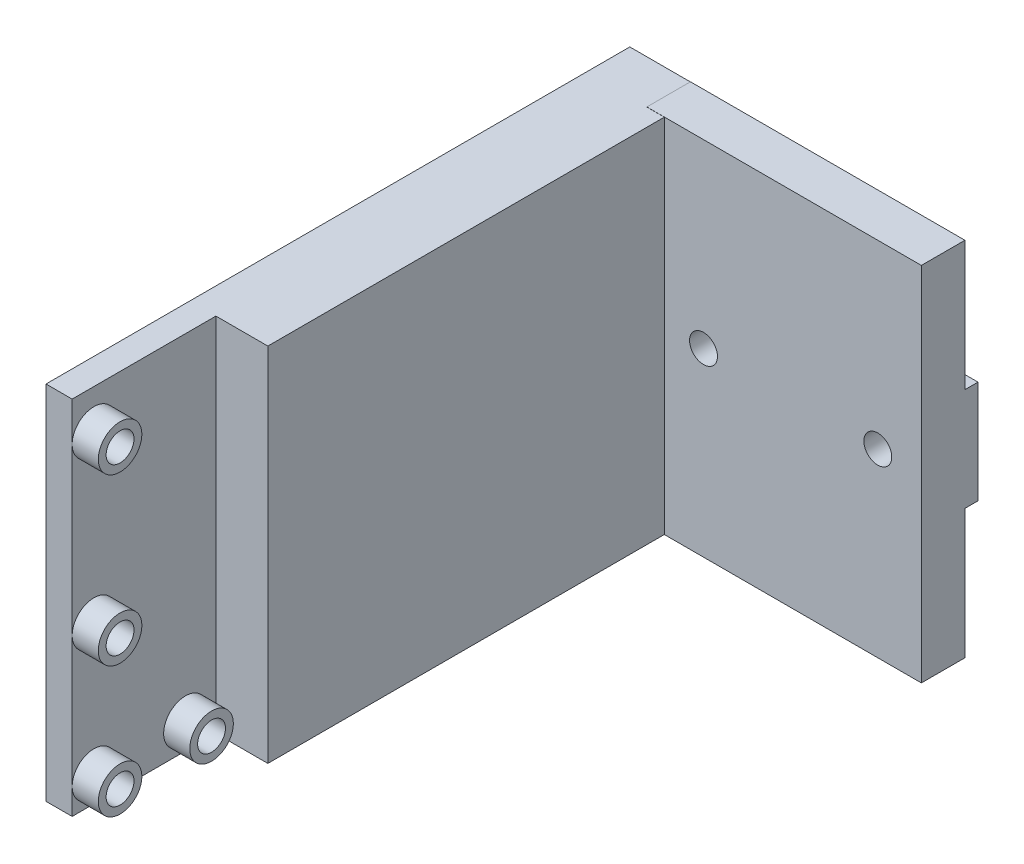
SolidWorks part; units mm, degrees
note: The reader was unsure of these and kept them because the rebuilt part matched: shared geometry of "Sketch4<6>".
ref_plane "Front Plane" through (0, 0, 0) normal (0, 0, 1) x (1, 0, 0)
ref_plane "Top Plane" through (0, 0, 0) normal (0, 1, 0) x (1, 0, 0)
ref_plane "Right Plane" through (0, 0, 0) normal (1, 0, 0) x (0, 0, -1)
sketch "Sketch1" plane through (0, 0, 0) normal (0, 0, 1) x (1, 0, 0)
  line L1 (-123.0401, -65.7341) -> (-91.5401, -65.7341)
  line L2 (-123.0401, -65.7341) -> (-123.0401, -107.2341)
  line L3 (-123.0401, -107.2341) -> (-91.5401, -107.2341)
  line L4 (-91.5401, -65.7341) -> (-91.5401, -107.2341)
  dimension "D2" = 41.5
  dimension "D1" = 31.5
extrude "Boss-Extrude1" add sketch "Sketch1" along normal blind 5
sketch "Sketch3" plane through (0, 0, 0) normal (0, 0, 1) x (1, 0, 0)
  line L1 (-123.0401, -65.75) -> (-129.0401, -65.75)
  line L2 (-123.0401, -65.75) -> (-123.0401, -107.2341)
  line L3 (-123.0401, -107.2341) -> (-129.0401, -107.2341)
  line L4 (-129.0401, -65.75) -> (-129.0401, -107.2341)
  line L6 (-123.0401, -107.2341) -> (-91.5401, -107.2341) construction
  line L7 (-123.0401, -65.7341) -> (-123.0401, -107.2341) construction
  dimension "D1" = 6
  dimension "D2" = 0
extrude "Boss-Extrude3" add sketch "Sketch3" along normal blind 50.5
sketch "Sketch5" plane through (0, 0, 50.5) normal (0, 0, 1) x (1, 0, 0)
  line L0 (-129.0401, -107.2341) -> (-123.0401, -107.2341) construction
  line L1 (-130, -65.75) -> (-127, -65.75)
  line L2 (-130, -65.75) -> (-130, -107.2341)
  line L3 (-130, -107.2341) -> (-127, -107.2341)
  line L4 (-127, -65.75) -> (-127, -107.2341)
  line L5 (-123.0401, -65.75) -> (-129.0401, -65.75) construction
  dimension "D1" = 0
  dimension "D2" = 3
  dimension "D3" = 0
extrude "Boss-Extrude4" add sketch "Sketch5" along normal blind 16.5
sketch "Sketch4" plane through (-127, 0, 0) normal (-1, 0, 0) x (0, 0, 1)
  line L0 (64.5, -104.25) -> (64.5, -70.25)
  line L3 (67, -107.2341) -> (67, -65.75) construction
  line L4 (54.5, -70.25) -> (64.5, -70.25)
  circle A0 centre (64.5, -70.25) radius 1.6
  circle A1 centre (64.5, -89.25) radius 1.6
  circle A2 centre (64.5, -104.25) radius 1.6
  circle A3 centre (54, -104.25) radius 1.6
  circle A4 centre (54, -104.25) radius 2.5
  circle A5 centre (64.5, -104.25) radius 2.5
  circle A6 centre (64.5, -89.25) radius 2.5
  circle A7 centre (64.5, -70.25) radius 2.5
  dimension "D1" = 3.2
  dimension "D2" = 3.2
  dimension "D3" = 3.2
  dimension "D4" = 3.2
  dimension "D5" = 5
  dimension "D6" = 5
  dimension "D7" = 5
  dimension "D8" = 5
  dimension "D10" = 15
  dimension "D13" = 19
  dimension "D9" = 10.5
  dimension "D11" = 2.5
sketch "Sketch6" plane through (-123.0401, 0, 0) normal (1, 0, 0) x (0, 0, -1)
  line L0 (-50.5, -107.2341) -> (-50.5, -65.75) construction
  line L1 (0, -107.2341) -> (-50.5, -107.2341)
  line L2 (0, -107.2341) -> (0, -65.75)
  line L3 (0, -65.75) -> (-50.5, -65.75)
  line L4 (-50.5, -107.2341) -> (-50.5, -65.75)
  line L5 (-50.5, -65.75) -> (-5, -65.75) construction
  line L6 (-5, -107.2341) -> (0, -107.2341) construction
  dimension "D1" = 0
  dimension "D2" = 0
  dimension "D3" = 0
extrude "Boss-Extrude6" add sketch "Sketch6" along normal blind 2
extrude "Boss-Extrude7" add sketch "Sketch4" against normal blind 3
extrude "Cut-Extrude1" cut sketch "Sketch4<6>" against normal through all both and the other way through all
sketch "Sketch4<6>" plane through (-127, 0, 0) normal (-1, 0, 0) x (0, 0, 1) same geometry as "Sketch4"
sketch "Sketch7" plane through (-91.5401, 0, 0) normal (1, 0, 0) x (0, 0, -1)
  line L0 (0, -107.2341) -> (0, -65.7341) construction
  line L1 (0, -92.3841) -> (1.5, -92.3841)
  line L2 (0, -92.3841) -> (0, -80.5841)
  line L3 (0, -80.5841) -> (1.5, -80.5841)
  line L4 (1.5, -92.3841) -> (1.5, -80.5841)
  line L5 (-5, -107.2341) -> (0, -107.2341) construction
  dimension "D1" = 1.5
  dimension "D2" = 11.8
  dimension "D3" = 14.85
extrude "Boss-Extrude8" add sketch "Sketch7" against normal up to surface (37.5 mm away) up to face at (-129.0401, -86.4921, 25.25)
sketch "Sketch8" plane through (0, 0, 5) normal (0, 0, 1) x (1, 0, 0)
  line L0 (-91.5401, -86.4841) -> (-121.0401, -86.4921) construction
  line L1 (-91.5401, -107.2341) -> (-91.5401, -65.7341) construction
  line L2 (-121.0401, -107.2341) -> (-121.0401, -65.75) construction
  circle A1 centre (-116.5401, -86.4908) radius 1.6
  circle A2 centre (-96.5401, -86.4855) radius 1.6
  dimension "D1" = 5
  dimension "D2" = 20
  dimension "D3" = 3.2
  dimension "D4" = 3.2
extrude "Cut-Extrude2" cut sketch "Sketch8" against normal through all
sketch "Sketch9" plane through (-129.0401, 0, 0) normal (-1, 0, 0) x (0, 0, 1)
  line L0 (50.5, -65.75) -> (0, -65.75)
  line L1 (0, -65.75) -> (0, -80.5841)
  line L2 (0, -80.5841) -> (-1.5, -80.5841)
  line L3 (-1.5, -80.5841) -> (-1.5, -92.3841)
  line L4 (-1.5, -92.3841) -> (0, -92.3841)
  line L5 (0, -92.3841) -> (0, -107.2341)
  line L6 (0, -107.2341) -> (50.5, -107.2341)
  line L7 (50.5, -107.2341) -> (50.5, -65.75)
extrude "Boss-Extrude9" add sketch "Sketch9" along normal up to surface (0.9599 mm away) up to face at (-130, -104.25, 52.4)
